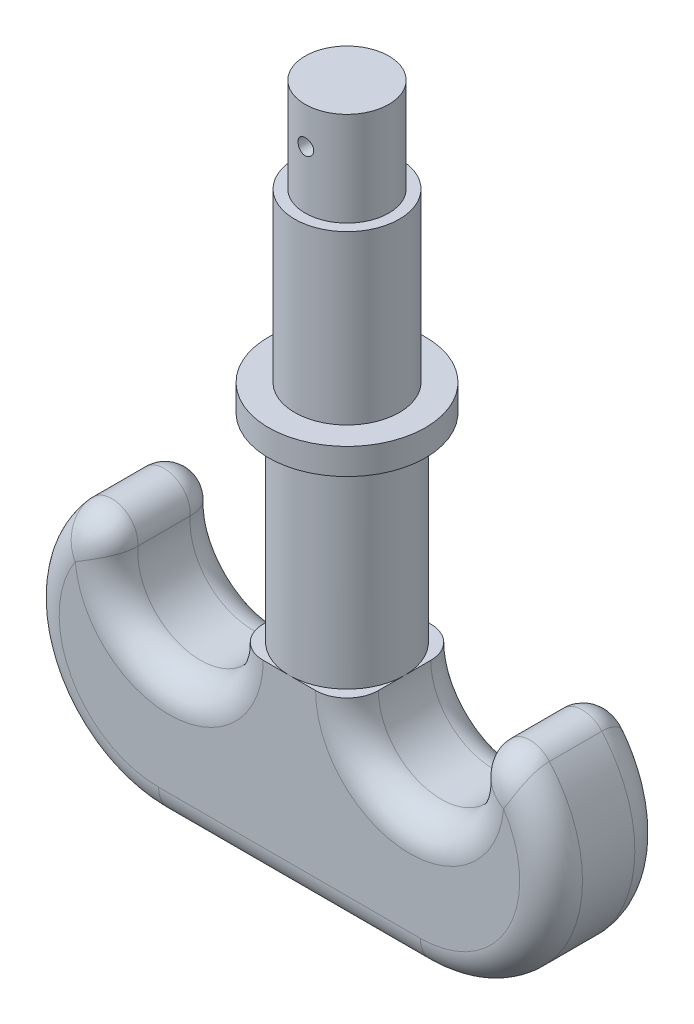
SolidWorks part; units mm, degrees
ref_plane "Front Plane" through (0, 0, 0) normal (0, 0, 1) x (1, 0, 0)
ref_plane "Top Plane" through (0, 0, 0) normal (0, 1, 0) x (1, 0, 0)
ref_plane "Right Plane" through (0, 0, 0) normal (1, 0, 0) x (0, 0, -1)
sketch "Sketch1" plane through (0, 0, 0) normal (0, 0, 1) x (1, 0, 0)
  line L0 (0, 0) -> (50, 0) construction
  line L1 (0, 0) -> (0, 54.1805) construction
  line L2 (-11.7401, 37) -> (11, 37)
  line L3 (15, 75) -> (0, 75)
  line L4 (15, 80) -> (0, 80)
  line L5 (10, 112) -> (0, 111.9949)
  line L6 (0, 111.9949) -> (0, 141.5957)
  line L7 (25, 0) -> (-25, 0)
  line L8 (11, 37) -> (11, 75)
  line L9 (0, 0) -> (0, 75)
  line L11 (15, 75) -> (15, 80)
  line L14 (0, 75) -> (0, 112)
  line L16 (10, 80) -> (10, 112)
  line L19 (0, 112) -> (0, 111.9949)
  line L21 (8, 111.9949) -> (8, 130)
  line L24 (8, 130) -> (0, 130)
  arc A0 (11, 37) -> (34.9657, 37.9061) centre (23, 37) ccw
  arc A1 (25, 0) -> (43.6893, 41.6045) centre (25, 25) ccw
  arc A2 (43.6893, 41.6045) -> (34.9657, 37.9061) centre (39.9515, 38.2836) ccw
  arc A3 (-25, 0) -> (-43.6893, 41.6045) centre (-25, 25) cw
  arc A4 (-43.6893, 41.6045) -> (-34.9657, 37.9061) centre (-39.9515, 38.2836) cw
  arc A5 (-11, 37) -> (-34.9657, 37.9061) centre (-23, 37) cw
  point P4 (0, 0)
  point P8 (0, 0)
  point P35 (0, 75)
  point P41 (0, 80)
  point P47 (0, 111.9949)
extrude "Boss-Extrude1" add sketch "Sketch1" along normal mid plane 22 contours L2 A5 A4 A3 L7 L9 | A1 A2 A0 L2 L9 L7 region at (-23.9645, 18.2977, 0) region at (23.9645, 18.2977, 0)
sketch "Sketch3" plane through (0, 0, 0) normal (0, 0, 1) x (1, 0, 0)
  line L0 (0, 37) -> (0, 188.4523) construction
  line L2 (-11, 37) -> (11, 37) construction
  line L3 (11, 37) -> (11, 75)
  line L4 (11, 75) -> (15, 75)
  line L5 (15, 75) -> (15, 80)
  line L6 (15, 80) -> (10, 80)
  line L7 (10, 80) -> (10, 112)
  line L8 (10, 112) -> (8, 112)
  line L9 (8, 112) -> (8, 130)
  line L10 (8, 130) -> (0, 130)
  line L11 (0, 130) -> (0, 37)
  line L12 (0, 37) -> (11, 37)
  dimension "D1" = 75
  dimension "D2" = 5
  dimension "D3" = 15
  dimension "D4" = 10
  dimension "D5" = 8
  dimension "D6" = 32
  dimension "D7" = 18
  dimension "D8" = 130
revolve "Revolve1" add sketch "Sketch3" angle 360 about L0
fillet "Fillet4" radius 6 14 edges at (47.8047, 14.7558, -11) (0, 0, -11) (-47.8047, 14.7558, -11) (47.8047, 14.7558, 11) (0, 0, 11) (-47.8047, 14.7558, 11) (37.9998, 42.887, 11) (37.9998, 42.887, -11) (-37.9998, 42.887, 11) (-37.9998, 42.887, -11) (23.4534, 25.0086, -11) (23.4534, 25.0086, 11) (-23.4534, 25.0086, -11) (-23.4534, 25.0086, 11)
sketch "Sketch4" plane through (0, 0, 0) normal (0, 0, 1) x (1, 0, 0)
  line L0 (8, 130) -> (-8, 130) construction
  circle A0 centre (0, 123) radius 1.5
  dimension "D1" = 7
  dimension "D2" = 3
  dimension "D3" = 123
extrude "Cut-Extrude2" cut sketch "Sketch4" against normal blind 15 and the other way blind 13
